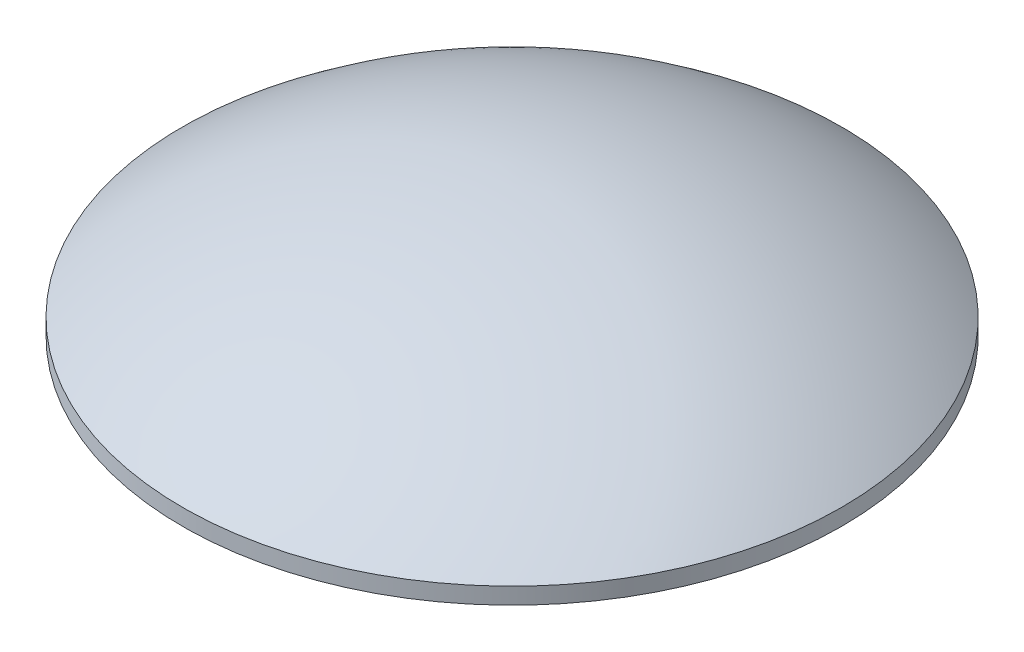
SolidWorks part; units mm, degrees
material "Стекло"
ref_plane "Спереди" through (0, 0, 0) normal (0, 0, 1) x (1, 0, 0)
ref_plane "Сверху" through (0, 0, 0) normal (0, 1, 0) x (1, 0, 0)
ref_plane "Справа" through (0, 0, 0) normal (1, 0, 0) x (0, 0, -1)
sketch "Эскиз1" plane through (0, 0, 0) normal (0, 0, 1) x (1, 0, 0)
  line L0 (0, 0) -> (30, 0)
  line L1 (0, 0) -> (0, 12)
  line L2 (30, 0) -> (30, 1.5)
  circle A2 centre (0, -36.1071) radius 48.1071
  dimension "D1" = 12
  dimension "D2" = 30
  dimension "D3" = 1.5
revolve "Повернуть1" add sketch "Эскиз1" angle 360 about L1 region at (12.051, 4.8781, 0)
